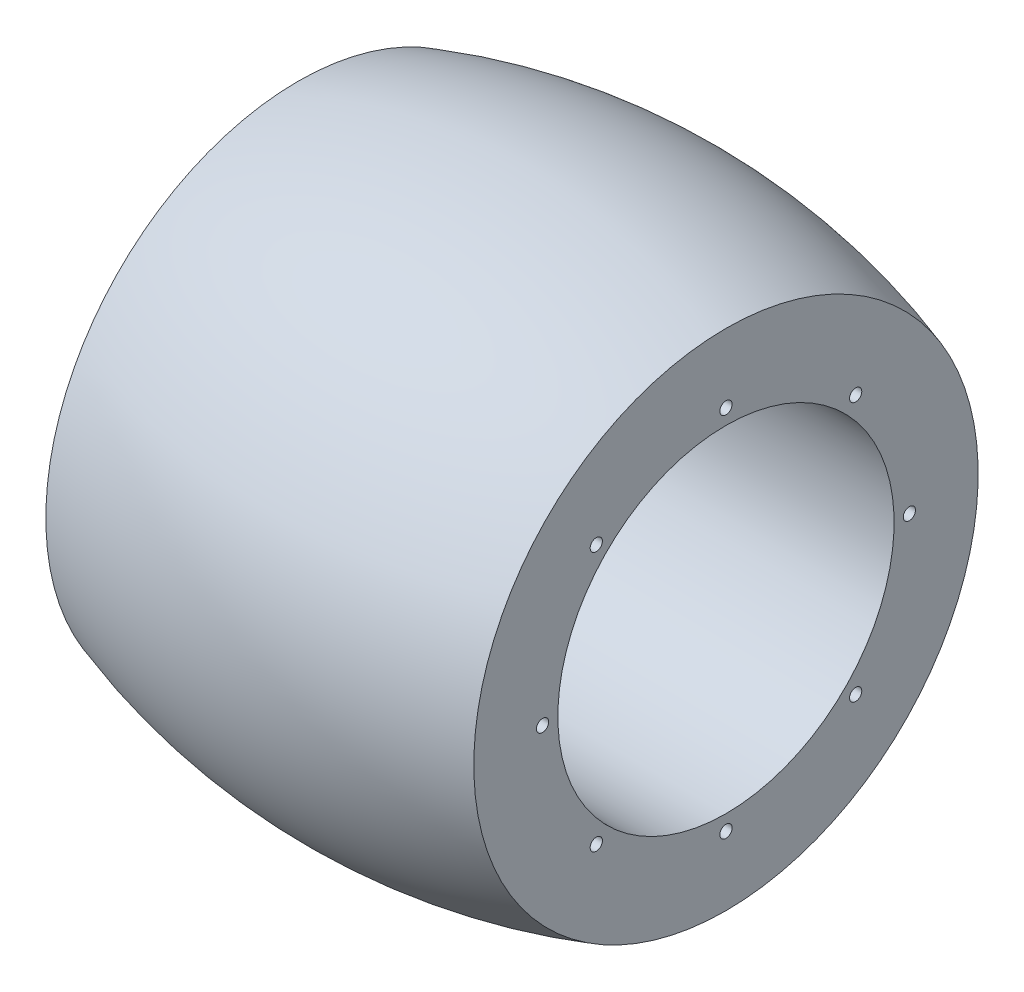
SolidWorks part; units mm, degrees
material "PVC hart"
ref_plane "Ebene vorne" through (0, 0, 0) normal (0, 0, 1) x (1, 0, 0)
ref_plane "Ebene oben" through (0, 0, 0) normal (0, 1, 0) x (1, 0, 0)
ref_plane "Ebene rechts" through (0, 0, 0) normal (1, 0, 0) x (0, 0, -1)
ref_axis "Achse" through (35.2, 0, 0) along (-1, 0, 0)
sketch "Skizze1" plane through (0, 0, 0) normal (0, 0, 1) x (1, 0, 0)
  line L0 (-26, 22) -> (26, 22)
  line L1 (-28, 33) -> (-28, 22)
  line L3 (-28, 22) -> (-26, 22)
  line L4 (0, 37.5) -> (0, 0) construction
  line L5 (0, 0) -> (-6.4519, 0) construction
  line L7 (28, 33) -> (28, 22)
  line L11 (-26, 22) -> (-26, 29.3041)
  line L13 (26, 22) -> (26, 29.3041)
  line L14 (26, 22) -> (28, 22)
  arc A0 (-28, 33) -> (28, 33) centre (0, -51.8611) cw
  arc A1 (-26, 29.3041) -> (-23.8179, 32.1905) centre (-23, 29.3041) cw
  arc A2 (-23.8179, 32.1905) -> (23.8179, 32.1905) centre (0, -51.8611) cw
  arc A3 (26, 29.3041) -> (23.8179, 32.1905) centre (23, 29.3041) ccw
  point P23 (0, 37.5)
  dimension "D1" = 75
  dimension "D4" = 89.3611
  dimension "D5" = 2
  dimension "D7" = 3
  dimension "D3" = 66
  dimension "D6" = 2
revolve "Rotation1" add sketch "Skizze1" angle 360 about L5 region at (0, 28.1438, 0) region at (-27, 22.5811, 0)
hole_wizard "Formsenkung für M3 Senkschraube mit Innensechskant2" positions "Skizze4" profile "Skizze5" countersink size "M3" standard "DIN"
sketch "Skizze4" plane through (32.5, -4.7475, 0) normal (-1, 0, 0) x (0, 0, 1)
  line L0 (0, 4.7475) -> (0, 26.7475) construction
  line L2 (0, 26.7475) -> (0, 28.7475) construction
  line L4 (0, 28.7475) -> (0, 30.7475) construction
  point P0 (0, 28.7475)
  point P25 (16.9706, 21.7181)
  point P26 (24, 4.7475)
  point P27 (16.9706, -12.223)
  point P28 (0, -19.2525)
  point P29 (-16.9706, -12.223)
  point P30 (-24, 4.7475)
  point P31 (-16.9706, 21.7181)
  point P32 (0, 4.7475)
sketch "Skizze5" plane through (32.5, 24, 0) normal (0, 1, 0) x (0, 0, -1)
  line L0 (0, 0) -> (0, 12.9807)
  line L1 (0, 12.9807) -> (0.8, 12.5)
  line L2 (0.8, 12.5) -> (0.8, 1.075)
  line L3 (0.8, 1.075) -> (1.875, 0)
  line L4 (1.875, 0) -> (0, 0)
  line L5 (-0.8, 1.075) -> (-1.875, 0) construction
  line L6 (0, 12.9807) -> (-0.8, 12.5) construction
  line L7 (0, -6.35) -> (0, 107.95) construction
  dimension "Bohrerdurchmesser" = 1.6
  dimension "Bohrungstiefe" = 12.5
  dimension "Senkdurchmesser (Oben)" = 3.75
  dimension "Senkwinkel (Oben)" = 90
  dimension "Spitzenwinkel" = 118
